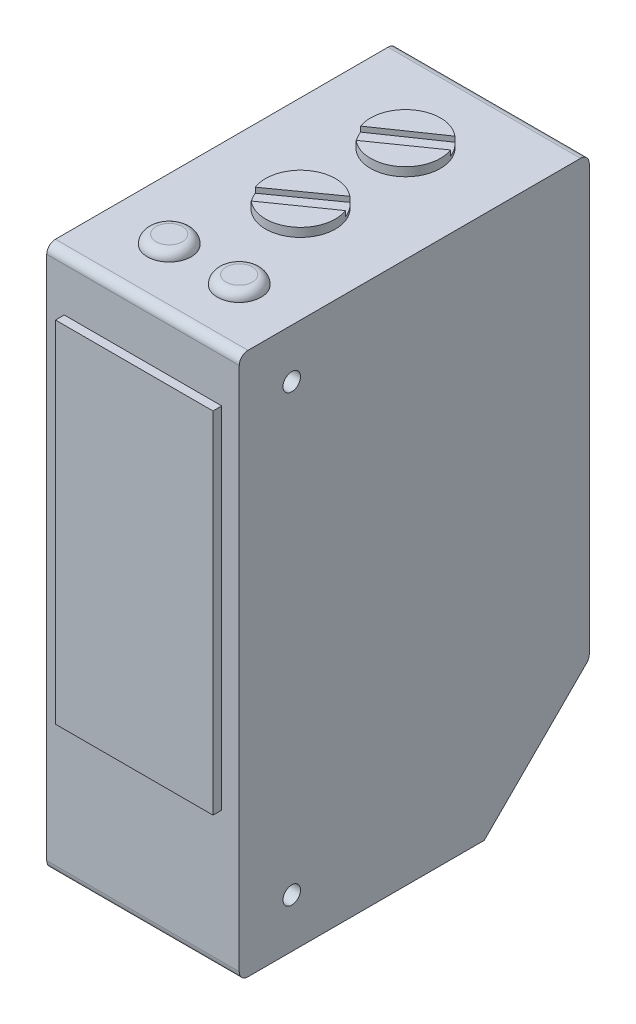
SolidWorks part; units mm, degrees
ref_plane "Front Plane" through (0, 0, 0) normal (0, 0, 1) x (1, 0, 0)
ref_plane "Top Plane" through (0, 0, 0) normal (0, 1, 0) x (1, 0, 0)
ref_plane "Right Plane" through (0, 0, 0) normal (1, 0, 0) x (0, 0, -1)
sketch "Sketch1" plane through (0, 0, 0) normal (1, 0, 0) x (0, 0, -1)
  line L0 (0, 0) -> (0, 31)
  line L1 (0, 31) -> (20, 31)
  line L2 (20, 31) -> (20, 6)
  line L3 (20, 6) -> (14, 0)
  line L4 (14, 0) -> (0, 0)
  dimension "D1" = 20
  dimension "D2" = 31
  dimension "D3" = 45
  dimension "D4" = 25
extrude "Boss-Extrude1" add sketch "Sketch1" along normal blind 11
sketch "Sketch2" plane through (11, 0, 0) normal (1, 0, 0) x (0, 0, -1)
  line L0 (0, 0) -> (14, 0) construction
  line L1 (0, 31) -> (0, 0) construction
  circle A0 centre (3, 2.8) radius 0.5
  circle A1 centre (3, 28.2) radius 0.5
  point P8 (3, 28.2)
  dimension "D1" = 1
  dimension "D2" = 25.4
  dimension "D3" = 2.8
  dimension "D4" = 3
extrude "Cut-Extrude1" cut sketch "Sketch2" against normal through all
sketch "Sketch3" plane through (0, 0, 0) normal (0, 0, 1) x (1, 0, 0)
  line L0 (11, 0) -> (0, 0) construction
  line L1 (1, 28) -> (10, 28)
  line L2 (1, 28) -> (1, 8)
  line L3 (1, 8) -> (10, 8)
  line L4 (10, 28) -> (10, 8)
  point P6 (5.5, 8)
  point P7 (5.5, 0)
  dimension "D1" = 20
  dimension "D2" = 8
  dimension "D3" = 9
extrude "Boss-Extrude2" add sketch "Sketch3" along normal blind 0.5 contours L2 L1 L4 L3
sketch "Sketch5" plane through (0, 31, 0) normal (0, 1, 0) x (1, 0, 0)
  line L0 (11, 20) -> (0, 20) construction
  line L1 (3.5, 3.5) -> (7.5, 3.5) construction
  line L2 (11, 0) -> (0, 0) construction
  circle A0 centre (3.5, 3.5) radius 1.25
  circle A1 centre (7.5, 3.5) radius 1.25
  circle A2 centre (5.5, 15) radius 2
  circle A3 centre (5.5, 9) radius 2
  point P10 (5.5, 20)
  point P11 (5.5, 3.5)
  point P12 (3.5, 3.1949)
  dimension "D1" = 4
  dimension "D2" = 4
  dimension "D4" = 2.5
  dimension "D3" = 6
  dimension "D5" = 4
  dimension "D6" = 5
  dimension "D7" = 3.5
extrude "Boss-Extrude3" add sketch "Sketch5" along normal blind 0.5
fillet "Fillet2" radius 0.5 1 edges at (3.5, 31.5, -2.25)
fillet "Fillet3" radius 0.5 1 edges at (7.5, 31.5, -2.25)
fillet "Fillet4" radius 0.5 1 edges at (5.5, 31, 0)
fillet "Fillet5" radius 0.5 1 edges at (5.5, 31, -20)
fillet "Fillet6" radius 0.5 1 edges at (5.5, 0, 0)
fillet "Fillet7" radius 0.5 1 edges at (5.5, 6, -20)
sketch "Sketch6" plane through (0, 31.5, 0) normal (0, 1, 0) x (1, 0, 0)
  line L0 (6.7862, 10.5316) -> (3.6331, 8.2825)
  line L1 (4.2005, 7.4797) -> (7.3731, 9.7011)
  line L2 (3.6209, 14.3152) -> (6.8127, 16.5089)
  line L3 (4.2005, 13.4797) -> (7.3731, 15.7011)
  circle A0 centre (5.5, 9) radius 2 construction
  circle A1 centre (5.5, 9) radius 2 construction
  arc A2 (3.6331, 8.2825) -> (4.2005, 7.4797) centre (5.5, 9) ccw
  arc A3 (7.3731, 15.7011) -> (6.8127, 16.5089) centre (5.5, 15) ccw
  circle A4 centre (5.5, 15) radius 2
  arc A5 (3.6209, 14.3152) -> (4.2005, 13.4797) centre (5.5, 15) ccw
  arc A6 (7.3731, 9.7011) -> (6.7862, 10.5316) centre (5.5, 9) ccw
  dimension "D1" = 0.5
  dimension "D2" = 0.5
  dimension "D3" = 55
  dimension "D5" = 0.5
  dimension "D6" = 55
  dimension "D4" = 0
extrude "Cut-Extrude3" cut sketch "Sketch6" against normal blind 0.3
